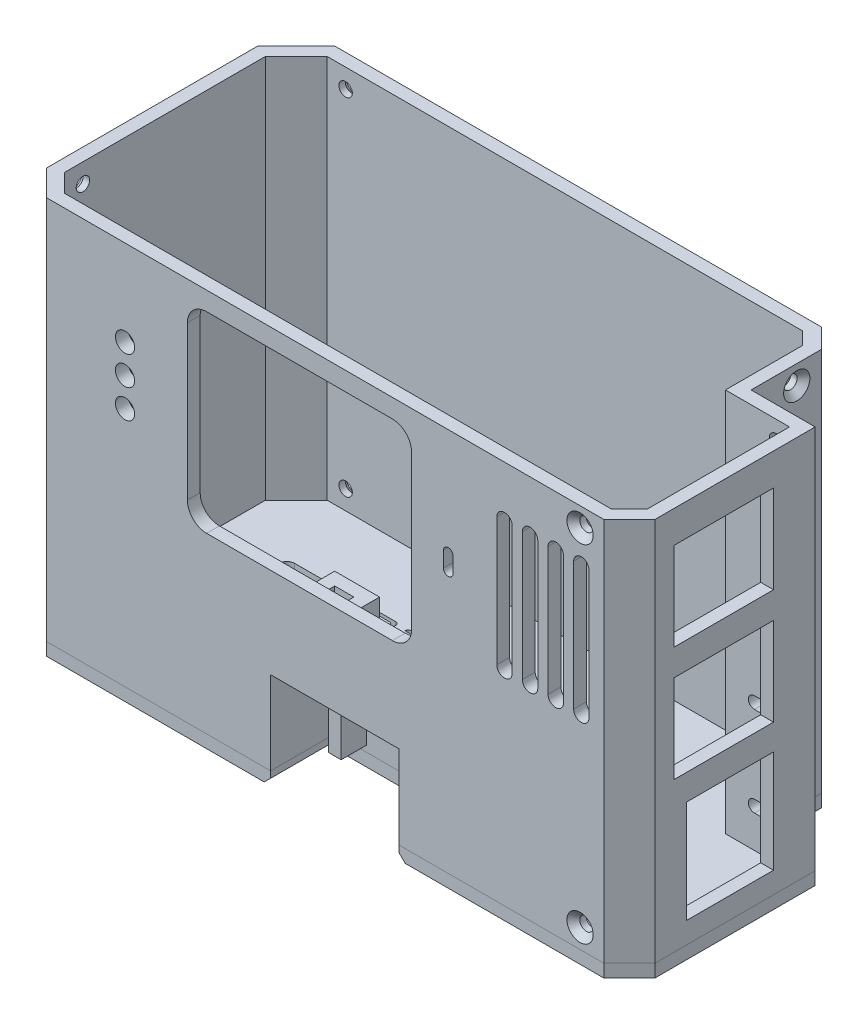
SolidWorks part; units mm, degrees
ref_plane "前视基准面" through (0, 0, 0) normal (0, 0, 1) x (1, 0, 0)
ref_plane "上视基准面" through (0, 0, 0) normal (0, 1, 0) x (1, 0, 0)
ref_plane "右视基准面" through (0, 0, 0) normal (1, 0, 0) x (0, 0, -1)
other "Configuration Table"
sketch "草图1" plane through (0, 0, 0) normal (0, 0, 1) x (1, 0, 0)
  line L1 (-105.5174, 35.9027) -> (-10.5174, 35.9027)
  line L2 (-105.5174, 35.9027) -> (-105.5174, -26.0973)
  line L3 (-105.5174, -26.0973) -> (-10.5174, -26.0973)
  line L4 (-10.5174, 35.9027) -> (-10.5174, -26.0973)
  dimension "D1" = 62
  dimension "D2" = 95
extrude "凸台-拉伸1" add sketch "草图1" along normal blind 43
sketch "草图4" plane through (0, -26.0973, 0) normal (0, -1, 0) x (1, 0, 0)
  line L0 (-10.5174, 43) -> (-10.5174, 0) construction
  line L1 (-10.5174, 14) -> (-20.5174, 14)
  line L2 (-10.5174, 14) -> (-10.5174, 0)
  line L3 (-10.5174, 0) -> (-20.5174, 0)
  line L4 (-20.5174, 14) -> (-20.5174, 0)
  line L5 (-105.5174, 0) -> (-10.5174, 0) construction
  dimension "D1" = 14
  dimension "D2" = 10
extrude "切除-拉伸3" cut sketch "草图4" against normal up to next
chamfer "倒角2" distance 6 angle 45 1 edges at (-105.5174, 4.9027, 0)
chamfer "倒角3" distance 4 angle 45 2 edges at (-105.5174, 4.9027, 43) (-10.5174, 4.9027, 43)
sketch "草图7" plane through (0, 0, 43) normal (0, 0, 1) x (1, 0, 0)
  line L0 (-101.5174, -26.0973) -> (-14.5174, -26.0973) construction
  line L1 (-46.5174, -26.0973) -> (-66.5174, -26.0973)
  line L2 (-46.5174, -26.0973) -> (-46.5174, -6.0973)
  line L3 (-46.5174, -6.0973) -> (-66.5174, -6.0973)
  line L4 (-66.5174, -26.0973) -> (-66.5174, -6.0973)
  line L6 (-10.5174, -26.0973) -> (-10.5174, 35.9027) construction
  dimension "D1" = 36
  dimension "D2" = 20
  dimension "D3" = 20
extrude "切除-拉伸5" cut sketch "草图7" against normal blind 10
shell "抽壳3" thickness 2 removed face at (-54.2952, 35.9027, 22)
sketch "草图9" plane through (0, -6.0973, 0) normal (0, -1, 0) x (1, 0, 0)
  line L0 (-44.5174, 41) -> (-68.5174, 41) construction
  line L1 (-46.5174, 41) -> (-66.5174, 41)
  line L2 (-46.5174, 41) -> (-46.5174, 33)
  line L3 (-46.5174, 33) -> (-66.5174, 33)
  line L4 (-66.5174, 41) -> (-66.5174, 33)
  line L5 (-66.5174, 33) -> (-46.5174, 33) construction
  line L8 (-66.5174, 33) -> (-66.5174, 43) construction
  line L9 (-46.5174, 33) -> (-46.5174, 43) construction
extrude "切除-拉伸6" cut sketch "草图9" against normal blind 10
sketch "草图10" plane through (0, -6.0973, 0) normal (0, -1, 0) x (1, 0, 0)
  line L4 (-66.5174, 43) -> (-66.5174, 41)
  line L5 (-66.5174, 41) -> (-46.5174, 41)
  line L6 (-46.5174, 41) -> (-46.5174, 43)
  line L7 (-46.5174, 43) -> (-66.5174, 43)
  line L8 (-66.5174, 43) -> (-66.5174, 41)
  line L9 (-66.5174, 41) -> (-46.5174, 41)
  line L10 (-46.5174, 41) -> (-46.5174, 43)
  line L11 (-46.5174, 43) -> (-66.5174, 43)
  dimension "D1" = 0
extrude "凸台-拉伸2" add sketch "草图10" along normal blind 5
sketch "草图11" plane through (0, 0, 43) normal (0, 0, 1) x (1, 0, 0)
  line L0 (-97.0174, 3.0227) -> (-76.0174, 3.0227) construction
  line L1 (-44.5121, 32.986) -> (-79.5174, 32.986)
  line L2 (-44.5121, 32.986) -> (-44.5121, 3.0227)
  line L3 (-44.5121, 3.0227) -> (-79.5174, 3.0227)
  line L4 (-79.5174, 32.986) -> (-79.5174, 3.0227)
  arc A0 (-44.0174, 32.8768) -> (-45.0174, 33.0227) centre (-45.0174, 29.5227) ccw construction
extrude "切除-拉伸7" cut sketch "草图11" against normal blind 2
fillet "圆角5" radius 3 4 edges at (-79.5174, 32.986, 42) (-79.5174, 3.0227, 42) (-44.5121, 32.986, 42) (-44.5121, 3.0227, 42)
sketch "草图12" plane through (0, 0, 33) normal (0, 0, 1) x (1, 0, 0)
  line L0 (-46.5174, -4.0973) -> (-66.5174, -4.0973) construction
  line L1 (-63.5174, -4.0973) -> (-49.5174, -4.0973)
  line L2 (-63.5174, -4.0973) -> (-63.5174, -23.0973)
  line L3 (-63.5174, -23.0973) -> (-49.5174, -23.0973)
  line L4 (-49.5174, -4.0973) -> (-49.5174, -23.0973)
  line L5 (-66.5174, -4.0973) -> (-66.5174, -11.0973) construction
  line L6 (-46.5174, -4.0973) -> (-46.5174, -11.0973) construction
  line L7 (-66.5174, -26.0973) -> (-46.5174, -26.0973) construction
  dimension "D1" = 3
  dimension "D2" = 3
  dimension "D3" = 3
extrude "凸台-拉伸3" add sketch "草图12" along normal blind 4
sketch "草图13" plane through (0, -4.0973, 0) normal (0, 1, 0) x (1, 0, 0)
  line L0 (-44.5174, -31) -> (-68.5174, -31) construction
  line L1 (-61.5174, -31) -> (-51.5174, -31)
  line L2 (-61.5174, -31) -> (-61.5174, -35.5752)
  line L3 (-61.5174, -35.5752) -> (-51.5174, -35.5752)
  line L4 (-51.5174, -31) -> (-51.5174, -35.5752)
  line L5 (-68.5174, -31) -> (-68.5174, -41) construction
  line L6 (-44.5174, -31) -> (-44.5174, -41) construction
  dimension "D1" = 7
  dimension "D2" = 7
extrude "切除-拉伸8" cut sketch "草图13" against normal blind 17
sketch "草图14" plane through (0, 0, 37) normal (0, 0, 1) x (1, 0, 0)
  line L0 (-63.5174, -23.0973) -> (-49.5174, -23.0973) construction
  line L1 (-61.5174, -4.0973) -> (-51.5174, -4.0973)
  line L2 (-61.5174, -4.0973) -> (-61.5174, -23.0973)
  line L3 (-61.5174, -23.0973) -> (-51.5174, -23.0973)
  line L4 (-51.5174, -4.0973) -> (-51.5174, -23.0973)
extrude "切除-拉伸9" cut sketch "草图14" against normal up to surface (4 mm away) up to face at (-56.5174, -14.3473, 33)
chamfer "倒角4" distance 1 angle 45 2 edges at (-66.5174, -26.0973, 38) (-46.5174, -26.0973, 38)
sketch "草图15" plane through (-10.5174, 0, 0) normal (1, 0, 0) x (0, 0, -1)
  line L1 (-34.05, -4.7773) -> (-20.5, -4.7773)
  line L2 (-34.05, -4.7773) -> (-34.05, -20.7773)
  line L3 (-34.05, -20.7773) -> (-20.5, -20.7773)
  line L4 (-20.5, -4.7773) -> (-20.5, -20.7773)
  line L5 (-36, 13.0027) -> (-20.5, 13.0027)
  line L6 (-36, 13.0027) -> (-36, -0.7573)
  line L7 (-36, -0.7573) -> (-20.5, -0.7573)
  line L8 (-20.5, 13.0027) -> (-20.5, -0.7573)
  line L9 (-36, 30.9027) -> (-20.5, 30.9027)
  line L10 (-36, 30.9027) -> (-36, 17.1427)
  line L11 (-36, 17.1427) -> (-20.5, 17.1427)
  line L12 (-20.5, 30.9027) -> (-20.5, 17.1427)
extrude "切除-拉伸10" cut sketch "草图15" against normal blind 2
sketch "草图16" plane through (0, 0, 43) normal (0, 0, 1) x (1, 0, 0)
  line L0 (-38.7974, 19.2043) -> (-38.7974, 16.8043) construction
  line L1 (-38.0444, 19.2043) -> (-38.0444, 16.8043)
  line L2 (-39.5504, 19.2043) -> (-39.5504, 16.8043)
  line L3 (-44.5121, 29.986) -> (-44.5121, 6.0227) construction
  line L5 (-44.5121, 18.0043) -> (-51.3378, 18.0043) construction
  line L6 (-10.5174, -26.0973) -> (-10.5174, 35.9027) construction
  arc A0 (-38.0444, 19.2043) -> (-39.5504, 19.2043) centre (-38.7974, 19.2043) ccw
  arc A1 (-39.5504, 16.8043) -> (-38.0444, 16.8043) centre (-38.7974, 16.8043) ccw
  point P2 (-38.7974, 18.0043)
  point P14 (-44.5121, 18.0043)
  dimension "D1" = 2.4
  dimension "D2" = 28.28
extrude "切除-拉伸11" cut sketch "草图16" against normal blind 2
sketch "草图17" plane through (0, -26.0973, 0) normal (0, -1, 0) x (1, 0, 0)
  line L0 (-105.5174, 39) -> (-105.5174, 6) construction
  line L1 (-93.9174, 13.067) -> (-84.4174, 13.067)
  line L2 (-93.9174, 13.067) -> (-93.9174, 16.567)
  line L3 (-93.9174, 16.567) -> (-84.4174, 16.567)
  line L4 (-84.4174, 13.067) -> (-84.4174, 16.567)
  line L6 (-93.9174, 20.3114) -> (-84.4174, 20.3114)
  line L7 (-93.9174, 20.3114) -> (-93.9174, 23.8114)
  line L8 (-93.9174, 23.8114) -> (-84.4174, 23.8114)
  line L9 (-84.4174, 20.3114) -> (-84.4174, 23.8114)
  line L10 (-78.1448, 23.5342) -> (-71.5448, 23.5342)
  line L11 (-78.1448, 23.5342) -> (-78.1448, 20.3114)
  line L12 (-78.1448, 20.3114) -> (-71.5448, 20.3114)
  line L13 (-71.5448, 23.5342) -> (-71.5448, 20.3114)
  line L14 (-64.6448, 23.6466) -> (-58.0448, 23.6466)
  line L15 (-64.6448, 23.6466) -> (-64.6448, 20.3114)
  line L16 (-64.6448, 20.3114) -> (-58.0448, 20.3114)
  line L17 (-58.0448, 23.6466) -> (-58.0448, 20.3114)
  line L19 (-83.4263, 17.1002) -> (-76.4263, 17.1002)
  line L20 (-83.4263, 17.1002) -> (-83.4263, 13.067)
  line L21 (-83.4263, 13.067) -> (-76.4263, 13.067)
  line L22 (-76.4263, 17.1002) -> (-76.4263, 13.067)
  line L23 (-74.9763, 17.1002) -> (-67.9763, 17.1002)
  line L24 (-74.9763, 17.1002) -> (-74.9763, 13.067)
  line L25 (-74.9763, 13.067) -> (-67.9763, 13.067)
  line L26 (-67.9763, 17.1002) -> (-67.9763, 13.067)
  line L27 (-51.5174, 16.567) -> (-43.9374, 16.567)
  line L28 (-51.5174, 16.567) -> (-51.5174, 13.767)
  line L29 (-51.5174, 13.767) -> (-43.9374, 13.767)
  line L30 (-43.9374, 16.567) -> (-43.9374, 13.767)
  line L31 (-63.5659, 16.567) -> (-52.9233, 16.567)
  line L32 (-63.5659, 16.567) -> (-63.5659, 14.767)
  line L33 (-63.5659, 14.767) -> (-52.9233, 14.767)
  line L34 (-52.9233, 16.567) -> (-52.9233, 14.767)
  dimension "D1" = 11.6
  dimension "D2" = 27.3726
  dimension "D3" = 6.9
  dimension "D4" = 6.6
  dimension "D5" = 7
  dimension "D6" = 1.45
  dimension "D7" = 9.5
  dimension "D8" = 3.5
  dimension "D9" = 2.8
  dimension "D10" = 54
  dimension "D11" = 7.58
  dimension "D12" = 1.4059
  dimension "D13" = 1.8
extrude "切除-拉伸12" cut sketch "草图17" against normal blind 2
chamfer "倒角9" distance 1 angle 45 12 edges at (-78.1448, -24.0973, 21.9228) (-74.8448, -24.0973, 23.5342) (-71.5448, -24.0973, 21.9228) (-74.8448, -24.0973, 20.3114) (-61.3448, -24.0973, 23.6466) (-64.6448, -24.0973, 21.979) (-58.0448, -24.0973, 21.979) (-61.3448, -24.0973, 20.3114) (-51.5174, -24.0973, 15.167) (-47.7274, -24.0973, 16.567) (-43.9374, -24.0973, 15.167) (-47.7274, -24.0973, 13.767)
fillet "圆角2" radius 1.2 8 edges at (-93.9174, -25.0973, 16.567) (-84.4174, -25.0973, 16.567) (-84.4174, -25.0973, 13.067) (-93.9174, -25.0973, 13.067) (-93.9174, -25.0973, 20.3114) (-93.9174, -25.0973, 23.8114) (-84.4174, -25.0973, 23.8114) (-84.4174, -25.0973, 20.3114)
fillet "圆角3" radius 0.5 18 edges at (-43.9374, -25.5973, 13.767) (-51.5174, -25.5973, 13.767) (-64.6448, -25.5973, 23.6466) (-58.0448, -25.5973, 23.6466) (-71.5448, -25.5973, 23.5342) (-78.1448, -25.5973, 23.5342) (-67.9763, -25.0973, 17.1002) (-74.9763, -25.0973, 17.1002) (-76.4263, -25.0973, 17.1002) (-83.4263, -25.0973, 17.1002) (-83.4263, -25.0973, 13.067) (-74.9763, -25.0973, 13.067) (-76.4263, -25.0973, 13.067) (-67.9763, -25.0973, 13.067) (-63.5659, -25.0973, 14.767) (-63.5659, -25.0973, 16.567) (-52.9233, -25.0973, 16.567) (-52.9233, -25.0973, 14.767)
chamfer "倒角7" distance 1 angle 45 6 edges at (-51.5174, -25.5973, 16.567) (-43.9374, -25.5973, 16.567) (-58.0448, -25.5973, 20.3114) (-64.6448, -25.5973, 20.3114) (-78.1448, -25.5973, 20.3114) (-71.5448, -25.5973, 20.3114)
sketch "草图18" plane through (0, 0, 43) normal (0, 0, 1) x (1, 0, 0)
  line L1 (-79.5174, 18.0043) -> (-81.9758, 18.0043) construction
  circle A0 centre (-89.2561, 13.5043) radius 1.5
  circle A1 centre (-89.2561, 18.0043) radius 1.5
  circle A2 centre (-89.2561, 22.5043) radius 1.5
  dimension "D3" = 3
  dimension "D2" = 3
extrude "切除-拉伸13" cut sketch "草图18" against normal blind 2
sketch "草图20" plane through (0, -24.0973, 0) normal (0, 1, 0) x (1, 0, 0)
  line L1 (-83.4263, -13.567) -> (-76.9263, -13.567)
  line L2 (-83.4263, -13.567) -> (-83.4263, -16.6002)
  line L3 (-83.4263, -16.6002) -> (-76.9263, -16.6002)
  line L4 (-76.9263, -13.567) -> (-76.9263, -16.6002)
  line L5 (-74.9763, -13.567) -> (-68.4763, -13.567)
  line L6 (-74.9763, -13.567) -> (-74.9763, -16.6002)
  line L7 (-74.9763, -16.6002) -> (-68.4763, -16.6002)
  line L8 (-68.4763, -13.567) -> (-68.4763, -16.6002)
extrude "凸台-拉伸4" add sketch "草图20" against normal blind 1
sketch "草图21" plane through (0, -25.0973, 0) normal (0, -1, 0) x (1, 0, 0)
  line L0 (-76.9263, 13.567) -> (-83.4263, 13.567) construction
  line L1 (-76.9263, 16.6002) -> (-80.9263, 16.6002)
  line L2 (-76.9263, 16.6002) -> (-76.9263, 13.567)
  line L3 (-76.9263, 13.567) -> (-80.9263, 13.567)
  line L4 (-80.9263, 16.6002) -> (-80.9263, 13.567)
  line L5 (-68.4763, 13.567) -> (-74.9763, 13.567) construction
  line L6 (-68.4763, 16.6002) -> (-72.4763, 16.6002)
  line L7 (-68.4763, 16.6002) -> (-68.4763, 13.567)
  line L8 (-68.4763, 13.567) -> (-72.4763, 13.567)
  line L9 (-72.4763, 16.6002) -> (-72.4763, 13.567)
  dimension "D1" = 4
extrude "凸台-拉伸5" add sketch "草图21" along normal up to surface (1 mm away) up to face at (-61.3448, -26.0973, 22.1299)
fillet "圆角4" radius 0.5 10 edges at (-74.9763, -25.0973, 15.0836) (-83.4263, -25.0973, 15.0836) (-80.9263, -25.5973, 13.567) (-80.9263, -25.5973, 16.6002) (-72.4763, -25.5973, 16.6002) (-72.4763, -25.5973, 13.567) (-68.4763, -25.0973, 16.6002) (-68.4763, -25.0973, 13.567) (-76.9263, -25.0973, 13.567) (-76.9263, -25.0973, 16.6002)
chamfer "倒角10" distance 2 angle 45 1 edges at (-22.5174, 5.9027, 2)
chamfer "倒角11" distance 3 angle 45 1 edges at (-20.5174, 4.9027, 0)
sketch "草图26" plane through (-20.5174, 0, 0) normal (1, 0, 0) x (0, 0, -1)
  line L0 (-10, 18.9027) -> (-10, -21.0973) construction
  line L1 (-8.6566, 18.9027) -> (-8.6566, -21.0973)
  line L2 (-11.3434, 18.9027) -> (-11.3434, -21.0973)
  line L3 (-14, -26.0973) -> (-3, -26.0973) construction
  line L5 (0, 35.9027) -> (0, -26.0973) construction
  arc A0 (-8.6566, 18.9027) -> (-11.3434, 18.9027) centre (-10, 18.9027) ccw
  arc A1 (-11.3434, -21.0973) -> (-8.6566, -21.0973) centre (-10, -21.0973) ccw
  point P2 (-10, -1.0973)
  dimension "D1" = 40
  dimension "D2" = 25
  dimension "D3" = 10
extrude "切除-拉伸15" cut sketch "草图26" against normal up to next
sketch "草图27" plane through (0, 0, 43) normal (0, 0, 1) x (1, 0, 0)
  line L1 (-18.0174, 27.9027) -> (-18.0174, 7.9027) construction
  line L8 (-16.8174, 27.9027) -> (-16.8174, 7.9027)
  line L17 (-19.2174, 27.9027) -> (-19.2174, 7.9027)
  line L25 (-14.5174, 35.9027) -> (-101.5174, 35.9027) construction
  line L28 (-10.5174, 35.9027) -> (-10.5174, -26.0973) construction
  line L31 (-22.0174, 27.9027) -> (-22.0174, 7.9027) construction
  line L34 (-20.8174, 27.9027) -> (-20.8174, 7.9027)
  line L37 (-23.2174, 27.9027) -> (-23.2174, 7.9027)
  line L38 (-26.0174, 27.9027) -> (-26.0174, 7.9027) construction
  line L39 (-24.8174, 27.9027) -> (-24.8174, 7.9027)
  line L40 (-27.2174, 27.9027) -> (-27.2174, 7.9027)
  line L41 (-30.0174, 27.9027) -> (-30.0174, 7.9027) construction
  line L42 (-28.8174, 27.9027) -> (-28.8174, 7.9027)
  line L43 (-31.2174, 27.9027) -> (-31.2174, 7.9027)
  arc A44 (-16.8174, 27.9027) -> (-19.2174, 27.9027) centre (-18.0174, 27.9027) ccw
  arc A45 (-19.2174, 7.9027) -> (-16.8174, 7.9027) centre (-18.0174, 7.9027) ccw
  arc A46 (-20.8174, 27.9027) -> (-23.2174, 27.9027) centre (-22.0174, 27.9027) ccw
  arc A47 (-23.2174, 7.9027) -> (-20.8174, 7.9027) centre (-22.0174, 7.9027) ccw
  arc A48 (-24.8174, 27.9027) -> (-27.2174, 27.9027) centre (-26.0174, 27.9027) ccw
  arc A49 (-27.2174, 7.9027) -> (-24.8174, 7.9027) centre (-26.0174, 7.9027) ccw
  arc A50 (-28.8174, 27.9027) -> (-31.2174, 27.9027) centre (-30.0174, 27.9027) ccw
  arc A51 (-31.2174, 7.9027) -> (-28.8174, 7.9027) centre (-30.0174, 7.9027) ccw
  point P2 (-18.0174, 17.9027)
  point P14 (-22.0174, 17.9027)
  point P21 (-26.0174, 17.9027)
  point P28 (-30.0174, 17.9027)
  dimension "D3" = 20
  dimension "D4" = 1.2
  dimension "D1" = 8
  dimension "D2" = 7.5
  dimension "D5" = 4
sketch "草图29" plane through (-105.5174, 0, 0) normal (-1, 0, 0) x (0, 0, 1)
  line L0 (39, -26.0973) -> (6, -26.0973) construction
  circle A0 centre (35.3017, 32.9027) radius 1.05
  circle A1 centre (35.3017, -21.0973) radius 1.2021
  dimension "D1" = 2.1
  dimension "D2" = 5
extrude "切除-拉伸18" cut sketch "草图29" against normal up to next
sketch "草图30" plane through (0, 0, 0) normal (0, 0, -1) x (-1, 0, 0)
  line L0 (99.5174, -26.0973) -> (23.5174, -26.0973) construction
  circle A0 centre (95.8191, 32.9027) radius 1.05
  circle A1 centre (95.8191, -21.0973) radius 1.05
  dimension "D1" = 2.1
  dimension "D2" = 5
extrude "切除-拉伸19" cut sketch "草图30" against normal up to next
sketch "草图31" plane through (-20.5174, 0, 0) normal (1, 0, 0) x (0, 0, -1)
  line L0 (-14, -26.0973) -> (-3, -26.0973) construction
  circle A0 centre (-6.8698, 32.9027) radius 1.05
  circle A1 centre (-6.8698, -21.0973) radius 1.05
  dimension "D1" = 2.1
  dimension "D2" = 5
extrude "切除-拉伸20" cut sketch "草图31" against normal up to next
sketch "草图32" plane through (0, 0, 14) normal (0, 0, -1) x (-1, 0, 0)
  line L0 (10.5174, -26.0973) -> (20.5174, -26.0973) construction
  circle A0 centre (14.6174, 32.9027) radius 1.05
  circle A1 centre (14.6174, -21.0973) radius 1.05
  dimension "D1" = 2.1
  dimension "D2" = 5
extrude "切除-拉伸21" cut sketch "草图32" against normal up to next
sketch "草图33" plane through (0, 0, 43) normal (0, 0, 1) x (1, 0, 0)
  line L1 (-45.5174, -26.0973) -> (-14.5174, -26.0973) construction
  circle A0 centre (-18.2157, 32.9027) radius 1.05
  circle A1 centre (-18.2157, -21.0973) radius 1.05
  dimension "D1" = 2.1
  dimension "D2" = 5
extrude "切除-拉伸22" cut sketch "草图33" against normal up to next
chamfer "倒角20" distance 1 angle 45 10 edges at (-96.8691, 32.9027, 0) (-105.5174, 31.8527, 35.3017) (-17.1657, 32.9027, 43) (-15.6674, 32.9027, 14) (-20.5174, 32.9027, 5.8198) (-17.1657, -21.0973, 43) (-15.6674, -21.0973, 14) (-96.8691, -21.0973, 0) (-105.5174, -22.2995, 35.3017) (-20.5174, -21.0973, 5.8198)
sketch "草图34" plane through (0, 0, 14) normal (0, 0, -1) x (-1, 0, 0)
  line L0 (18.0174, -4.0973) -> (14.0174, -4.0973) construction
  line L1 (18.0174, -5.0973) -> (14.0174, -5.0973)
  line L2 (18.0174, -3.0973) -> (14.0174, -3.0973)
  line L3 (18.0174, -18.0973) -> (14.0174, -18.0973) construction
  line L4 (18.0174, -19.0973) -> (14.0174, -19.0973)
  line L5 (18.0174, -17.0973) -> (14.0174, -17.0973)
  line L7 (20.5174, 35.9027) -> (20.5174, -26.0973) construction
  arc A0 (18.0174, -5.0973) -> (18.0174, -3.0973) centre (18.0174, -4.0973) ccw
  arc A1 (14.0174, -3.0973) -> (14.0174, -5.0973) centre (14.0174, -4.0973) ccw
  arc A2 (18.0174, -19.0973) -> (18.0174, -17.0973) centre (18.0174, -18.0973) ccw
  arc A3 (14.0174, -17.0973) -> (14.0174, -19.0973) centre (14.0174, -18.0973) ccw
  point P3 (16.0174, -4.0973)
  point P8 (16.0174, -18.0973)
  dimension "D1" = 1
  dimension "D2" = 4
  dimension "D3" = 2.5
  dimension "D4" = 14
extrude "切除-拉伸25" cut sketch "草图34" against normal up to next (2 mm away) draft 2
extrude "切除-拉伸26" cut sketch "草图27" against normal up to next
split "分割1" bodies to split 138 resulting bodies 139 140 split by face at (-47.7274, -24.0973, 15.167)
